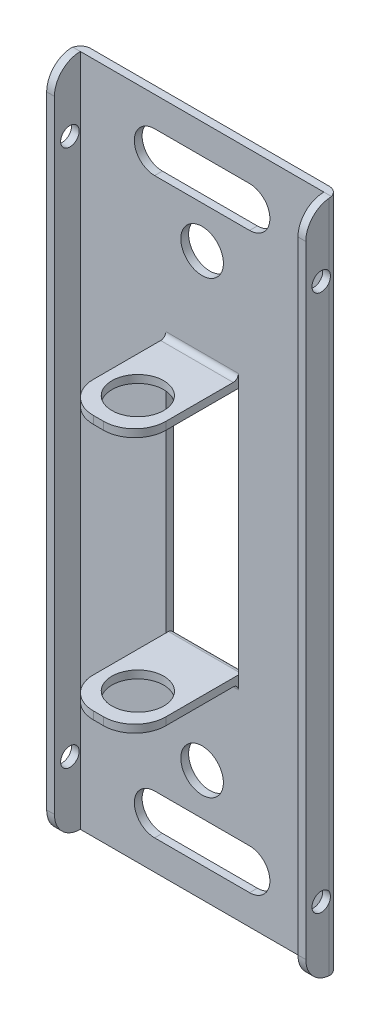
SolidWorks part; units mm, degrees
material "Plain Carbon Steel"
ref_plane "Спереди" through (0, 0, 0) normal (0, 0, 1) x (1, 0, 0)
ref_plane "Сверху" through (0, 0, 0) normal (0, 1, 0) x (1, 0, 0)
ref_plane "Справа" through (0, 0, 0) normal (1, 0, 0) x (0, 0, -1)
other "Configuration Table"
sketch "Sketch1" plane through (0, 0, 0) normal (0, 0, 1) x (1, 0, 0)
  line L0 (9.165, 55.3376) -> (-9.165, 55.3376) construction
  line L1 (25, -65) -> (-25, -65)
  line L2 (25, -65) -> (25, 65)
  line L3 (25, 65) -> (-25, 65)
  line L4 (-25, -65) -> (-25, 65)
  line L5 (25, -65) -> (-25, 65) construction
  line L6 (25, 65) -> (-25, -65) construction
  line L7 (7, -23.94) -> (-7, -23.94)
  line L8 (7, -23.94) -> (7, 23.94)
  line L9 (7, 23.94) -> (-7, 23.94)
  line L10 (-7, -23.94) -> (-7, 23.94)
  line L11 (7, -23.94) -> (-7, 23.94) construction
  line L12 (7, 23.94) -> (-7, -23.94) construction
  line L13 (9.165, 51.4247) -> (-9.165, 51.4247)
  line L14 (9.165, 59.2504) -> (-9.165, 59.2504)
  line L15 (-25, 0) -> (25, 0) construction
  line L18 (9.165, -55.3376) -> (-9.165, -55.3376) construction
  line L19 (9.165, -51.4247) -> (-9.165, -51.4247)
  line L20 (9.165, -59.2504) -> (-9.165, -59.2504)
  arc A0 (9.165, 51.4247) -> (9.165, 59.2504) centre (9.165, 55.3376) ccw
  arc A1 (-9.165, 59.2504) -> (-9.165, 51.4247) centre (-9.165, 55.3376) ccw
  circle A2 centre (0, 43.4034) radius 4.1085
  arc A5 (9.165, -51.4247) -> (9.165, -59.2504) centre (9.165, -55.3376) cw
  arc A6 (-9.165, -59.2504) -> (-9.165, -51.4247) centre (-9.165, -55.3376) cw
  circle A7 centre (0, -43.4034) radius 4.1085
  point P0 (0, 0)
  point P6 (0, 0)
  point P13 (0, 55.3376)
  point P24 (0, -55.3376)
  dimension "D1" = 50
  dimension "D2" = 130
  dimension "D3" = 14
  dimension "D4" = 47.88
extrude "Boss-Extrude1" add sketch "Sketch1" along normal blind 1.5
sketch "Sketch2" plane through (0, 0, 1.5) normal (0, 0, 1) x (1, 0, 0)
  line L0 (-25, 65) -> (-23.5, 65)
  line L1 (25, 65) -> (-25, 65) construction
  line L2 (-23.5, 65) -> (-23.5, -65)
  line L3 (-25, -65) -> (25, -65) construction
  line L4 (-23.5, -65) -> (-25, -65)
  line L5 (-25, -65) -> (-25, 65)
  line L6 (0, 65) -> (0, -65) construction
  line L7 (23.5, -65) -> (25, -65)
  line L8 (23.5, 65) -> (23.5, -65)
  line L9 (25, 65) -> (23.5, 65)
  line L10 (25, -65) -> (25, 65)
  dimension "D1" = 1.5
extrude "Boss-Extrude2" add sketch "Sketch2" along normal blind 5
sketch "Sketch3" plane through (25, 0, 0) normal (1, 0, 0) x (0, 0, -1)
  line L0 (0, 0) -> (-6.5, 0) construction
  line L1 (-6.5, -65) -> (-6.5, 65) construction
  circle A0 centre (-3.5093, 51.8362) radius 1.7889
  circle A1 centre (-3.5093, -51.8362) radius 1.7889
extrude "Cut-Extrude1" cut sketch "Sketch3" against normal through all
fillet "Fillet1" radius 5 4 edges at (-24.25, -65, 6.5) (24.25, -65, 6.5) (24.25, 65, 6.5) (-24.25, 65, 6.5)
fillet "Fillet2" radius 2 2 edges at (25, 0, 0) (-25, 0, 0)
sketch "Sketch4" plane through (0, 0, 1.5) normal (0, 0, 1) x (1, 0, 0)
  line L0 (-7, 23.94) -> (-7, 25.44)
  line L1 (-7, 23.94) -> (7, 23.94)
  line L2 (7, 23.94) -> (7, 25.44)
  line L3 (7, 25.44) -> (-7, 25.44)
  line L4 (7, 0) -> (-7, 0) construction
  line L5 (7, -23.94) -> (7, 23.94) construction
  line L6 (-7, 23.94) -> (-7, -23.94) construction
  line L7 (-7, -23.94) -> (-7, -25.44)
  line L8 (7, -23.94) -> (7, -25.44)
  line L9 (-7, -23.94) -> (7, -23.94)
  line L10 (7, -25.44) -> (-7, -25.44)
  dimension "D1" = 1.5
extrude "Boss-Extrude3" add sketch "Sketch4" along normal blind 20
fillet "Fillet3" radius 6 4 edges at (-7, -24.69, 21.5) (7, -24.69, 21.5) (7, 24.69, 21.5) (-7, 24.69, 21.5)
fillet "Fillet4" radius 1 4 edges at (0, -25.44, 1.5) (0, -23.94, 0) (0, 25.44, 1.5) (0, 23.94, 0)
sketch "Sketch5" plane through (0, 25.44, 0) normal (0, 1, 0) x (1, 0, 0)
  circle A0 centre (0, -13.9047) radius 5
  dimension "D1" = 10
extrude "Cut-Extrude2" cut sketch "Sketch5" against normal through all
